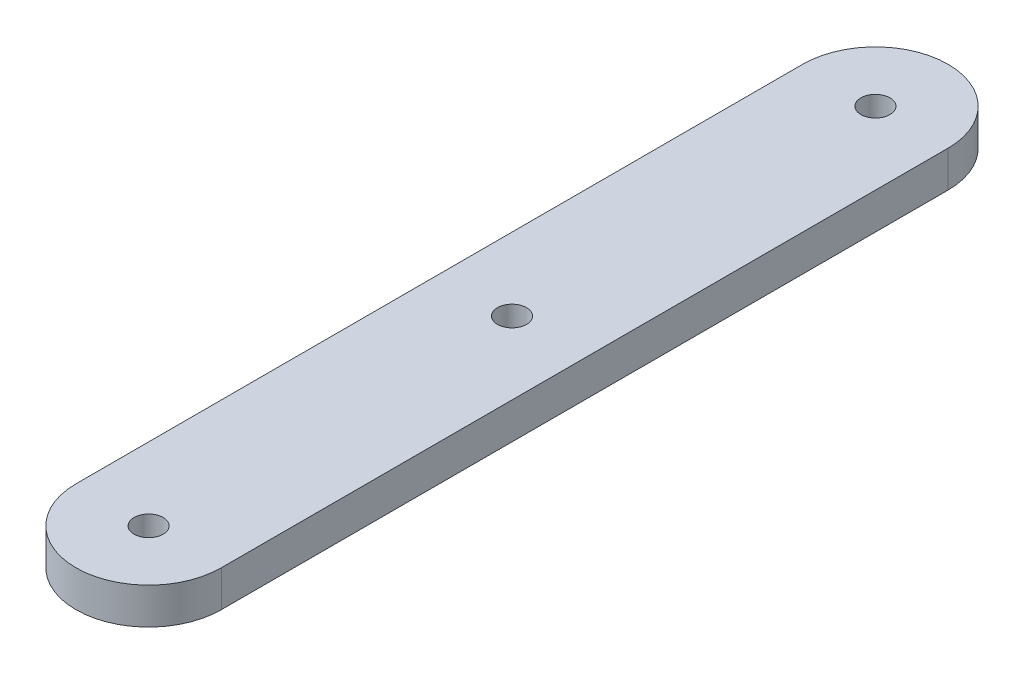
SolidWorks part; units mm, degrees
material "Polylactic Acid (PLA)"
ref_plane "Front Plane" through (0, 0, 0) normal (0, 0, 1) x (1, 0, 0)
ref_plane "Top Plane" through (0, 0, 0) normal (0, 1, 0) x (1, 0, 0)
ref_plane "Right Plane" through (0, 0, 0) normal (1, 0, 0) x (0, 0, -1)
sketch "Sketch2" plane through (0, 0, 0) normal (0, 1, 0) x (1, 0, 0)
  line L2 (-6.35, -31.75) -> (-6.35, 31.75)
  line L4 (6.35, -31.75) -> (6.35, 31.75)
  arc A0 (-6.35, 31.75) -> (6.35, 31.75) centre (0, 31.75) cw
  arc A1 (6.35, -31.75) -> (-6.35, -31.75) centre (0, -31.75) cw
  circle A2 centre (0, 31.75) radius 1.27
  circle A3 centre (0, -31.75) radius 1.27
  circle A4 centre (0, 0) radius 1.27
  dimension "D3" = 2.54
  dimension "D4" = 2.54
  dimension "D5" = 2.54
  dimension "D1" = 63.5
  dimension "D2" = 12.7
  dimension "D6" = 31.75
extrude "Boss-Extrude1" add sketch "Sketch2" along normal blind 3.175 contours A1 L4 A0 L2 A3 A2 region at (-5.5775, 0, 0)
equation "\"D6@Sketch2\"=\"D1@Sketch2\"/2"
